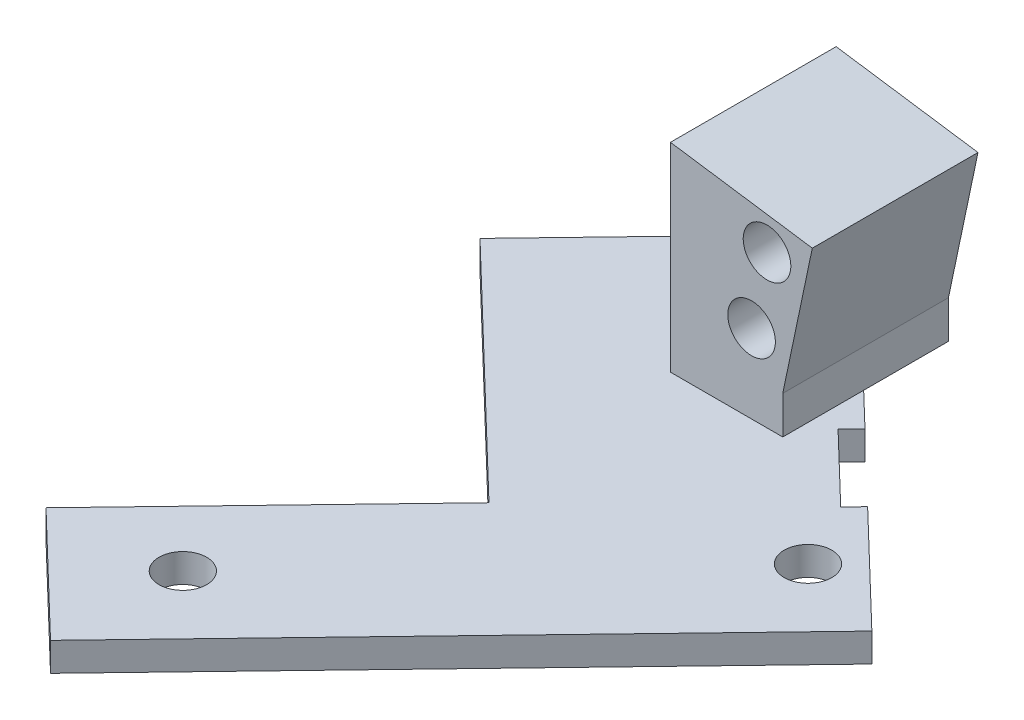
SolidWorks part; units mm, degrees
ref_plane "Front Plane" through (0, 0, 0) normal (0, 0, 1) x (1, 0, 0)
ref_plane "Top Plane" through (0, 0, 0) normal (0, 1, 0) x (1, 0, 0)
ref_plane "Right Plane" through (0, 0, 0) normal (1, 0, 0) x (0, 0, -1)
sketch "Sketch1" plane through (0, 0, 0) normal (0, 0, 1) x (1, 0, 0)
  line L0 (-629.0113, 228.5148) -> (-646.4173, 232.1744)
  line L1 (-625.5069, 227.7779) -> (-640.2031, 230.8679) construction
  line L2 (-646.4173, 232.1744) -> (-650.3578, 213.4325)
  line L3 (-650.3578, 213.4325) -> (-632.9518, 209.7729)
  line L4 (-626.0822, 208.3286) -> (-644.038, 212.1038) construction
  line L5 (-632.9518, 209.7729) -> (-629.0113, 228.5148)
  circle A0 centre (-635.0536, 225) radius 3.175
  circle A1 centre (-637.1112, 215.214) radius 3.175
  dimension "D4" = 6.35
  dimension "D5" = 6.35
  dimension "D1" = 6.35
  dimension "D2" = 19.1516
  dimension "D3" = 17.7865
extrude "Boss-Extrude1" add sketch "Sketch1" along normal up to surface (22.098 mm away)
sketch "Sketch2" plane through (15.4424, 73.4471, 0) normal (-0.2058, -0.9786, 0) x (0.9786, -0.2058, 0)
  line L0 (-680.3571, 22.098) -> (-680.3571, 0)
  line L1 (-680.3571, 0) -> (-673.9925, 0)
  line L2 (-680.3571, 0) -> (-662.5706, 0) construction
  line L3 (-673.9925, 0) -> (-673.9925, 22.098)
  line L4 (-662.5706, 22.098) -> (-680.3571, 22.098) construction
  line L5 (-673.9925, 22.098) -> (-680.3571, 22.098)
  dimension "D1" = 6.3646
extrude "Boss-Extrude2" add sketch "Sketch2" along normal blind 8.89 contours L5 L0 L1 L3
ref_plane "Plane5" through (0, 204.7328, 0) normal (0, 1, 0) x (1, 0, 0)
sketch "Sketch12" plane through (0, 204.7328, 0) normal (0, 1, 0) x (1, 0, 0)
  line L4 (-673.9093, -79.3977) -> (-658.2914, -94.4137)
  line L5 (-651.3433, 6.3746) -> (-676.0774, -19.351)
  line L6 (-904.3151, 142.1279) -> (780.195, -1477.4584) construction
  line L7 (-658.2914, -94.4137) -> (-604.5985, -38.5685)
  line L8 (-604.5985, -38.5685) -> (-651.3433, 6.3746)
  line L9 (-676.0774, -19.351) -> (-644.9506, -49.2781)
  line L10 (-644.9506, -49.2781) -> (-673.9093, -79.3977)
  circle A0 centre (-657.4844, -77.5717) radius 3.175
  circle A1 centre (-616.6175, -35.0666) radius 3.175
  dimension "D5" = 43.18
  dimension "D7" = 6.35
  dimension "D10" = 6.35
  dimension "D2" = 35.6873
  dimension "D3" = 77.47
  dimension "D4" = 90
  dimension "D6" = 3.81
  dimension "D8" = 45.72
extrude "Boss-Extrude6" add sketch "Sketch12" against normal blind 3.81
sketch "Sketch19" plane through (0, 0, 22.098) normal (0, 0, 1) x (1, 0, 0)
  line L0 (-646.4173, 232.1744) -> (-654.0373, 232.1744)
  line L1 (-654.0373, 232.1744) -> (-654.0373, 204.7328)
  line L2 (-673.9093, 204.7328) -> (-658.2914, 204.7328) construction
  line L3 (-654.0373, 204.7328) -> (-652.1869, 204.7328)
  line L4 (-652.1869, 204.7328) -> (-646.4173, 232.1744)
  dimension "D1" = 7.62
extrude "Boss-Extrude12" add sketch "Sketch19" against normal up to surface (22.098 mm away) up to face at (-641.73, 215.3418, 0)
sketch "Sketch20" plane through (0, 0, 0) normal (0, 0, -1) x (-1, 0, 0)
  line L0 (629.0113, 228.5148) -> (654.0373, 232.1744)
  line L1 (654.0373, 232.1744) -> (646.4173, 232.1744)
  line L2 (646.4173, 232.1744) -> (629.0113, 228.5148)
extrude "Cut-Extrude1" cut sketch "Sketch20" against normal blind 35.052
sketch "Sketch21" plane through (0, 0, 0) normal (0, 0, -1) x (-1, 0, 0)
  line L0 (644.1294, 212.123) -> (644.1294, 204.7328)
  line L1 (419.4444, 204.7328) -> (-419.4444, 204.7328) construction
  line L2 (644.1294, 204.7328) -> (645.6832, 204.7328)
  line L3 (645.6832, 204.7328) -> (644.1294, 212.123) construction
  line L4 (645.6832, 204.7328) -> (644.1294, 212.123)
extrude "Boss-Extrude13" add sketch "Sketch21" against normal blind 22.098
sketch "Sketch22" plane through (0, 204.7328, 0) normal (0, 1, 0) x (1, 0, 0)
  line L4 (-644.1294, 0) -> (-644.1294, -22.098)
  line L5 (-632.9518, 0) -> (-644.1294, 0)
  line L6 (-632.9518, -22.098) -> (-632.9518, 0)
  line L7 (-644.1294, -22.098) -> (-632.9518, -22.098)
  line L8 (-644.1294, 0) -> (-644.1294, -22.098)
  line L9 (-632.9518, 0) -> (-644.1294, 0)
  line L10 (-632.9518, -22.098) -> (-632.9518, 0)
  line L11 (-644.1294, -22.098) -> (-632.9518, -22.098)
  dimension "D1" = 0
extrude "Boss-Extrude14" add sketch "Sketch22" along normal up to body
sketch "Sketch23" plane through (0, 0, 22.098) normal (0, 0, 1) x (1, 0, 0)
  line L0 (-647.9291, 231.2812) -> (-647.9291, 204.7328)
  line L1 (-629.0113, 228.5148) -> (-654.0373, 232.1744) construction
  line L2 (-654.0373, 204.7328) -> (-632.9518, 204.7328) construction
  line L3 (-647.9291, 204.7328) -> (-654.0373, 204.7328)
  line L4 (-654.0373, 204.7328) -> (-654.0373, 232.1744)
  line L5 (-654.0373, 232.1744) -> (-654.0373, 204.7328) construction
  line L6 (-654.0373, 232.1744) -> (-647.9291, 231.2812)
extrude "Cut-Extrude3" cut sketch "Sketch23" against normal blind 39.878
sketch "Sketch24" plane through (0, 204.7328, 0) normal (0, 1, 0) x (1, 0, 0)
  line L0 (-619.2465, -24.4852) -> (-621.0069, -26.3161)
  line L1 (-604.5985, -38.5685) -> (-632.9518, -11.308) construction
  line L2 (-621.0069, -26.3161) -> (-630.1618, -17.5141)
  line L3 (-630.1618, -17.5141) -> (-628.4014, -15.6831)
  line L4 (-628.4014, -15.6831) -> (-619.2465, -24.4852)
  line L5 (-658.2914, -94.4137) -> (-604.5985, -38.5685) construction
  dimension "D1" = 12.7
  dimension "D2" = 2.54
  dimension "D3" = 20.32
extrude "Cut-Extrude4" cut sketch "Sketch24" against normal through all
